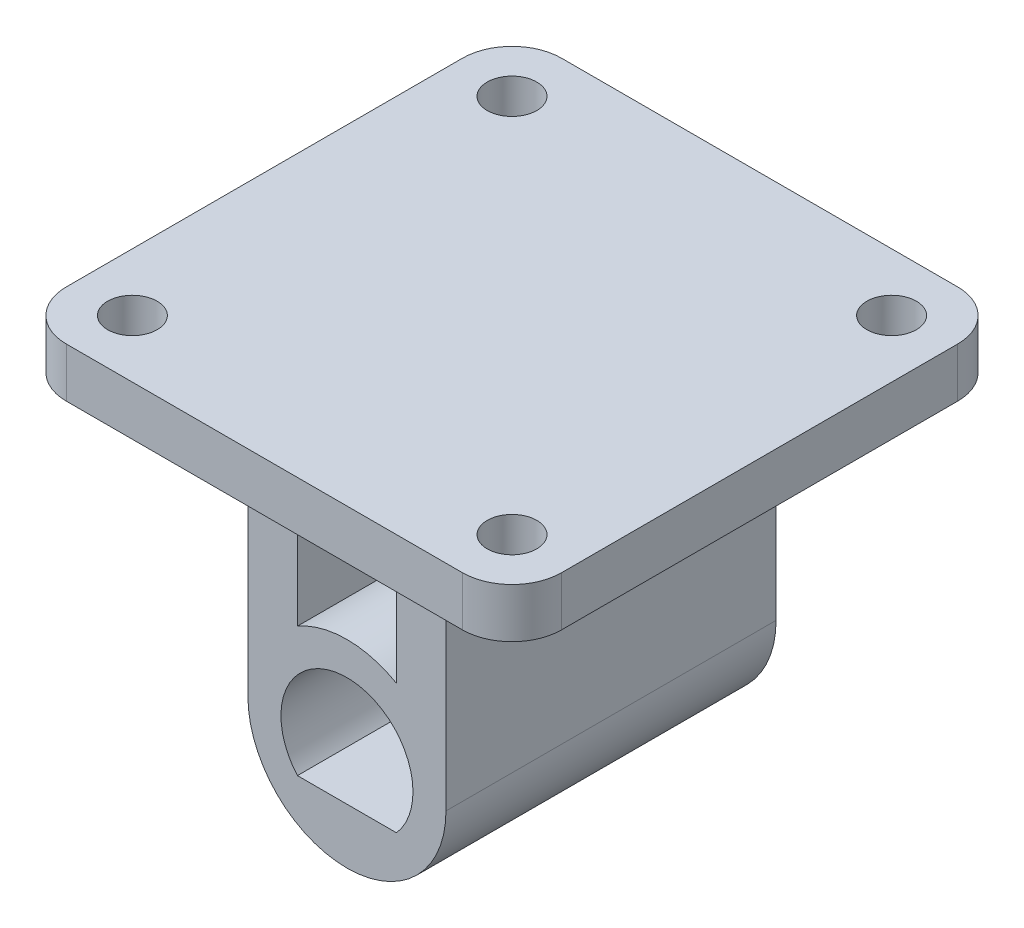
SolidWorks part; units mm, degrees
ref_plane "Alzado" through (0, 0, 0) normal (0, 0, 1) x (1, 0, 0)
ref_plane "Planta" through (0, 0, 0) normal (0, 1, 0) x (1, 0, 0)
ref_plane "Vista lateral" through (0, 0, 0) normal (1, 0, 0) x (0, 0, -1)
sketch "Croquis1" plane through (0, 0, 0) normal (0, 1, 0) x (1, 0, 0)
  line L0 (0, 0) -> (8.5714, 0) construction
  line L1 (0, 0) -> (0, -8.3442) construction
  line L2 (-15, 15) -> (15, 15)
  line L3 (15, 15) -> (15, -15)
  line L4 (15, -15) -> (-15, -15)
  line L5 (-15, -15) -> (-15, 15)
  dimension "D1" = 30
  dimension "D2" = 30
extrude "Saliente-Extruir1" add sketch "Croquis1" along normal blind 3
ref_plane "Plano1" through (0, 0, 10) normal (0, 0, 1) x (1, 0, 0)
sketch "Croquis3" plane through (0, 0, 10) normal (0, 0, 1) x (1, 0, 0)
  line L0 (0, 0) -> (0, 4.8812) construction
  line L5 (0, 0) -> (0, -9.5797) construction
  line L6 (-3, 0) -> (-3, -9.8038)
  line L11 (-6, 0) -> (-6, -15)
  line L12 (-15, 0) -> (15, 0) construction
  line L13 (6, -15) -> (6, 0)
  line L14 (6, 0) -> (3, 0)
  line L17 (-3, 0) -> (-6, 0)
  line L19 (3, -9.8038) -> (3, 0)
  line L20 (-3, -17.6458) -> (3, -17.6458)
  arc A2 (-6, -15) -> (6, -15) centre (0, -15) ccw
  arc A8 (-3, -9.8038) -> (3, -9.8038) centre (0, -15) cw
  arc A9 (3, -17.6458) -> (-3, -17.6458) centre (0, -15) ccw
  point P9 (-2.5993, -17.7004)
  point P14 (0, 0)
  point P16 (0, 0)
  point P17 (-3.1557, -10.8522)
  dimension "D1" = 6
  dimension "D3" = 15
  dimension "D5" = 6
  dimension "D4" = 6
  dimension "D8" = 3
  dimension "D6" = 6
  dimension "D2" = 4
  dimension "D7" = 6
extrude "Saliente-Extruir2" add sketch "Croquis3" against normal blind 20
sketch "Croquis4" plane through (0, 3, 0) normal (0, 1, 0) x (1, 0, 0)
  line L0 (0, 0) -> (-3.4922, 0) construction
  line L1 (0, 0) -> (0, 4.1707) construction
  circle A0 centre (-11.5, 11.5) radius 1.5
  circle A1 centre (11.5, 11.5) radius 1.5
  circle A2 centre (11.5, -11.5) radius 1.5
  circle A3 centre (-11.5, -11.5) radius 1.5
  point P8 (0, 0)
  point P13 (0, 0)
  point P14 (0, 0)
  point P15 (0, 0)
  point P16 (0, 0)
  dimension "D1" = 3
  dimension "D2" = 3
  dimension "D3" = 3
  dimension "D4" = 3
  dimension "D5" = 23
  dimension "D6" = 23
extrude "Cortar-Extruir1" cut sketch "Croquis4" against normal through all
fillet "Redondeo2" radius 3 4 edges at (15, 1.5, -15) (-15, 1.5, -15) (15, 1.5, 15) (-15, 1.5, 15)
fillet "Redondeo4" radius 2 2 edges at (-3, 0, 0) (3, 0, 0)
fillet "Redondeo5" radius 3 6 edges at (3.5, 0, -10) (-3.5, 0, -10) (-3.5, 0, 10) (3.5, 0, 10) (6, 0, 0) (-6, 0, 0)
